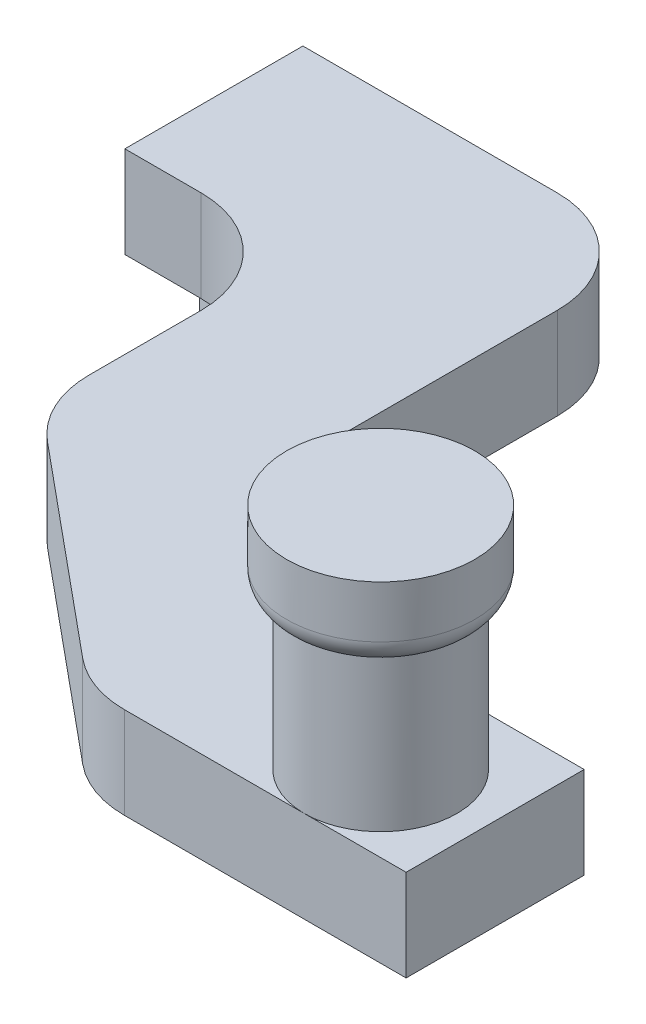
SolidWorks part; units mm, degrees
ref_plane "Front Plane" through (0, 0, 0) normal (0, 0, 1) x (1, 0, 0)
ref_plane "Top Plane" through (0, 0, 0) normal (0, 1, 0) x (1, 0, 0)
ref_plane "Right Plane" through (0, 0, 0) normal (1, 0, 0) x (0, 0, -1)
sketch "Sketch1" plane through (0, 0, 0) normal (0, 1, 0) x (1, 0, 0)
  line L0 (0, 0) -> (7, 0)
  line L1 (7, 0) -> (7, -7)
  line L2 (7, -7) -> (10.0804, -9.5517)
  line L3 (10.0804, -9.5517) -> (15.0804, -9.5517)
  line L4 (0, -3.5) -> (3.5, -3.5)
  line L5 (3.5, -3.5) -> (3.5, -8.6456)
  line L6 (3.5, -8.6456) -> (8.8191, -13.0517)
  line L7 (8.8191, -13.0517) -> (15.0804, -13.0517)
  line L8 (15.0804, -9.5517) -> (15.0804, -13.0517)
  line L9 (0, 0) -> (0, -3.5)
  dimension "D1" = 7
  dimension "D2" = 7
  dimension "D3" = 4
  dimension "D4" = 5
  dimension "D5" = 3.5
extrude "Boss-Extrude1" add sketch "Sketch1" along normal blind 1.8
fillet "Fillet1" radius 2 5 edges at (7, 0.9, 7) (3.5, 0.9, 8.6456) (3.5, 0.9, 3.5) (7, 0.9, 0) (8.8191, 0.9, 13.0517)
sketch "Sketch2" plane through (0, 1.8, 0) normal (0, 1, 0) x (1, 0, 0)
  line L0 (15.0804, -9.5517) -> (10.0804, -9.5517) construction
  line L1 (15.0804, -13.0517) -> (15.0804, -9.5517) construction
  circle A0 centre (13.0804, -11.5517) radius 1.5
  dimension "D1" = 2
  dimension "D2" = 2
extrude "Boss-Extrude2" add sketch "Sketch2" along normal blind 3
sketch "Sketch3" plane through (0, 4.8, 0) normal (0, 1, 0) x (1, 0, 0)
  circle A0 centre (13.0804, -11.5517) radius 1.85
extrude "Boss-Extrude3" add sketch "Sketch3" along normal blind 1.5
fillet "Fillet2" radius 0.5 1 edges at (13.0804, 4.8, 13.4017)
sketch "Sketch4" plane through (0, 0, 0) normal (0, -1, 0) x (-1, 0, 0)
  circle A0 centre (-1.5563, -1.4668) radius 1.5
extrude "Boss-Extrude4" add sketch "Sketch4" along normal blind 2.5
sketch "Sketch5" plane through (0, -2.5, 0) normal (0, -1, 0) x (1, 0, 0)
  circle A0 centre (1.5536, 1.4529) radius 1.72
extrude "Boss-Extrude5" add sketch "Sketch5" along normal blind 1
fillet "Fillet3" radius 0.5 1 edges at (1.5536, -2.5, -0.2671)
